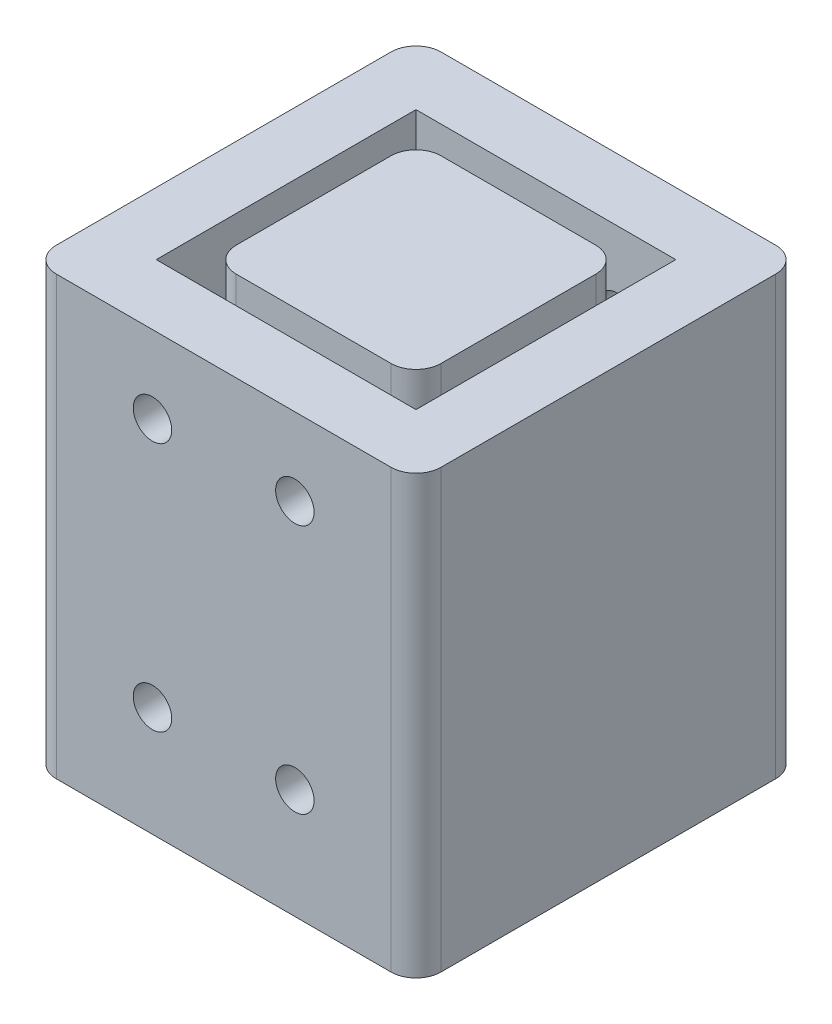
SolidWorks part; units mm, degrees
ref_plane "Front Plane" through (0, 0, 0) normal (0, 0, 1) x (1, 0, 0)
ref_plane "Top Plane" through (0, 0, 0) normal (0, 1, 0) x (1, 0, 0)
ref_plane "Right Plane" through (0, 0, 0) normal (1, 0, 0) x (0, 0, -1)
sketch "Sketch1" plane through (0, 0, 0) normal (0, 1, 0) x (1, 0, 0)
  line L0 (-19.558, -19.558) -> (19.558, -19.558)
  line L1 (-13.208, -13.208) -> (13.208, -13.208)
  line L2 (-13.208, -13.208) -> (-13.208, 13.208)
  line L3 (-13.208, 13.208) -> (13.208, 13.208)
  line L4 (13.208, -13.208) -> (13.208, 13.208)
  line L5 (-13.208, -13.208) -> (13.208, 13.208) construction
  line L6 (-13.208, 13.208) -> (13.208, -13.208) construction
  line L7 (19.558, -19.558) -> (19.558, 19.558)
  line L8 (-19.558, 19.558) -> (19.558, 19.558)
  line L9 (-19.558, -19.558) -> (-19.558, 19.558)
  line L11 (10.414, 10.414) -> (-10.414, 10.414)
  line L12 (10.414, 10.414) -> (10.414, -10.414)
  line L13 (10.414, -10.414) -> (-10.414, -10.414)
  line L14 (-10.414, 10.414) -> (-10.414, -10.414)
  line L15 (10.414, 10.414) -> (-10.414, -10.414) construction
  line L16 (10.414, -10.414) -> (-10.414, 10.414) construction
  point P0 (0, 0)
  point P10 (0, 0)
  dimension "D1" = 26.416
  dimension "D2" = 6.35
  dimension "D3" = 20.828
  dimension "D4" = 20.828
extrude "Boss-Extrude1" add sketch "Sketch1" along normal blind 38.1 contours L11 L14 L13 L12 | L9 L0 L7 L8 L4 L1 L2 L3 region at (-19.0048, 0, 0) region at (0, 0, 0)
sketch "Sketch2" plane through (0, 0, 19.558) normal (0, 0, 1) x (1, 0, 0)
  line L1 (0, 38.1) -> (0, 0) construction
  line L3 (-19.558, 0) -> (19.558, 0) construction
  circle A0 centre (-7.239, 30.226) radius 1.9558
  circle A1 centre (7.239, 30.226) radius 1.9558
  circle A2 centre (7.239, 4.826) radius 1.9558
  circle A3 centre (-7.239, 4.826) radius 1.9558
  dimension "D1" = 25.4
  dimension "D2" = 3.9116
  dimension "D3" = 4.826
  dimension "D4" = 14.478
  dimension "D5" = 7.239
extrude "Cut-Extrude1" cut sketch "Sketch2" against normal through all
extrude "Boss-Extrude2" add sketch "Sketch1<2>" against normal blind 6.35 contours L11 L14 L13 L12 | L1 L4 L3 L2 L14 L11 L12 L13 | L9 L0 L7 L8 L4 L1 L2 L3 region at (-19.0048, 0, 0) region at (-12.8344, 0, 0) region at (0, 0, 0)
sketch "Sketch1<2>" plane through (0, 0, 0) normal (0, 1, 0) x (1, 0, 0) same geometry as "Sketch1"
fillet "Fillet1" radius 2.54 8 edges at (19.558, 15.875, -19.558) (-19.558, 15.875, -19.558) (19.558, 15.875, 19.558) (-19.558, 15.875, 19.558) (-10.414, 19.05, -10.414) (10.414, 19.05, 10.414) (-10.414, 19.05, 10.414) (10.414, 19.05, -10.414)
